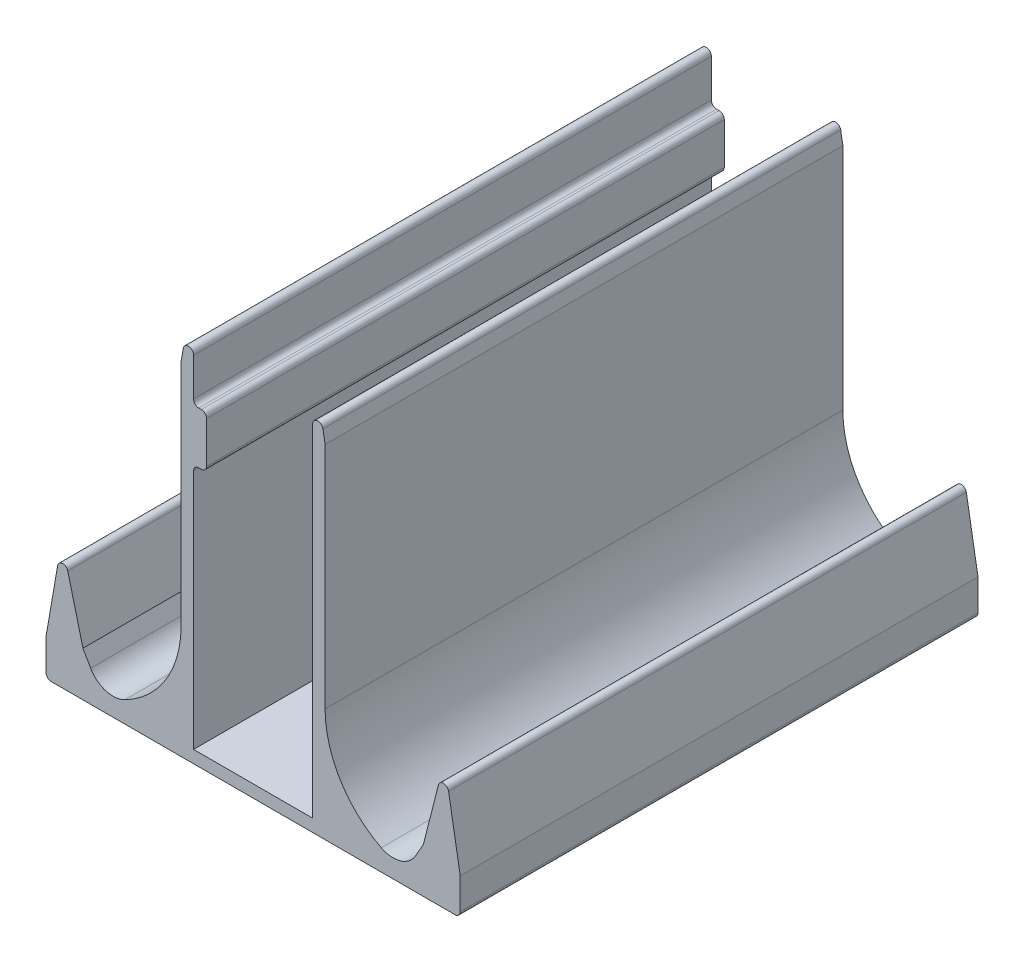
SolidWorks part; units mm, degrees
ref_plane "Plan de face" through (0, 0, 0) normal (0, 0, 1) x (1, 0, 0)
ref_plane "Plan de dessus" through (0, 0, 0) normal (0, 1, 0) x (1, 0, 0)
ref_plane "Plan de droite" through (0, 0, 0) normal (1, 0, 0) x (0, 0, -1)
sketch "Esquisse1" plane through (0, 0, 0) normal (0, 0, 1) x (1, 0, 0)
  line L0 (-11.5, 2.4) -> (11.5, 2.4)
  line L1 (11.5, 2.4) -> (11.5, 80)
  line L3 (40, 0) -> (-40, 0)
  line L4 (0, 0) -> (0, 138.9113) construction
  line L5 (-11.5, 2.4) -> (-11.5, 50)
  line L7 (-11.5, 50) -> (-9, 50)
  line L8 (-9, 50) -> (-9, 60)
  line L9 (-9, 60) -> (-11.5, 60)
  line L10 (-11.5, 60) -> (-11.5, 80)
  line L11 (13.9, 66.1116) -> (13.9, 2.4)
  line L12 (13.9, 2.4) -> (29.296, 2.4)
  line L14 (-13.9, 2.4) -> (-29.296, 2.4)
  line L15 (-13.9, 66.1116) -> (-13.9, 2.4)
  line L17 (-11.5, 80) -> (-13.9, 66.1116)
  line L18 (-40, 7.0079) -> (-40, 0)
  line L19 (40, 0) -> (40, 7.0079)
  line L20 (11.5, 80) -> (13.9, 66.1116)
  line L21 (-40, 7.0079) -> (-36.9546, 24.6314)
  line L23 (40, 7.0079) -> (36.9546, 24.6314)
  line L25 (-36.9546, 24.6314) -> (-32.8662, 8.6468)
  line L26 (-32.8662, 8.6468) -> (-29.296, 2.4)
  line L27 (32.8662, 8.6468) -> (29.296, 2.4)
  line L28 (36.9546, 24.6314) -> (32.8662, 8.6468)
  point P3 (0, 2.4)
  point P26 (-40, 6.4989)
  point P27 (-36.6131, 23.2964)
  point P28 (-40, 7.0079)
  dimension "D1" = 23
  dimension "D2" = 80
  dimension "D3" = 80
  dimension "D4" = 2.4
  dimension "D5" = 2.5
  dimension "D6" = 10
  dimension "D7" = 20
  dimension "D8" = 2.4
  dimension "D10" = 2.4
extrude "Boss.-Extru.1" add sketch "Esquisse1" along normal blind 100
fillet "Congé2" radius 1 4 edges at (-11.5, 60, 50) (-9, 60, 50) (-9, 50, 50) (-11.5, 50, 50)
fillet "Conges_base" radius 20 2 edges at (13.9, 2.4, 50) (-13.9, 2.4, 50)
fillet "Congé4" radius 1 6 edges at (11.5, 80, 50) (-11.5, 80, 50) (40, 0, 50) (-40, 0, 50) (36.9546, 24.6314, 50) (-36.9546, 24.6314, 50)
fillet "Congé5" radius 5 2 edges at (29.296, 2.4, 50) (-29.296, 2.4, 50)
equation "\"ep\"= 2.4"
equation "\"D4@Esquisse1\"=\"ep\""
equation "\"D10@Esquisse1\"=\"ep\""
equation "\"D8@Esquisse1\"=\"ep\""
